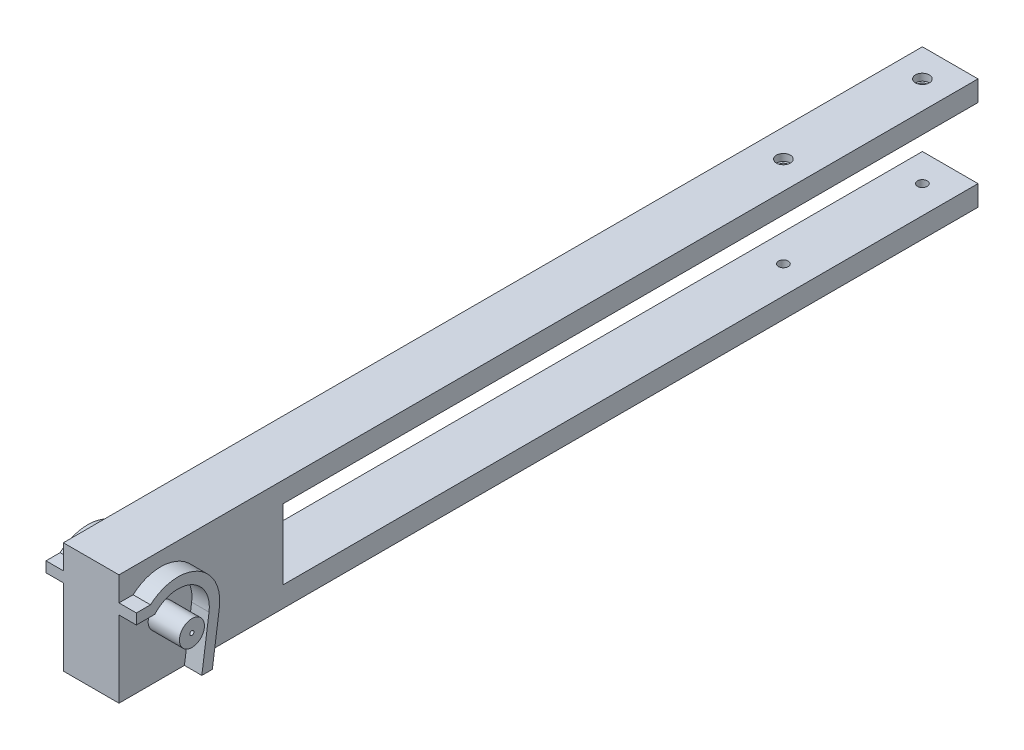
SolidWorks part; units mm, degrees
ref_plane "前视基准面" through (0, 0, 0) normal (0, 0, 1) x (1, 0, 0)
ref_plane "上视基准面" through (0, 0, 0) normal (0, 1, 0) x (1, 0, 0)
ref_plane "右视基准面" through (0, 0, 0) normal (1, 0, 0) x (0, 0, -1)
other "Configuration Table"
sketch "草图2" plane through (0, 0, 0) normal (1, 0, 0) x (0, 0, -1)
  line L0 (-6, 0) -> (17.6, 0) construction
  line L1 (-6, 8) -> (17.6, 8)
  line L2 (-6, 8) -> (-6, -8)
  line L3 (-6, -8) -> (17.6, -8)
  line L4 (17.6, 8) -> (17.6, -8)
  line L5 (1.8, 8) -> (1.8, -8)
  line L6 (4.4562, -0.6263) -> (3.4199, -8)
  line L7 (0, -4.5) -> (-6, -4.5)
  line L8 (0, -4.5) -> (0, 3)
  line L9 (0, 3) -> (-6, 3)
  line L10 (-6, -4.5) -> (-6, 3)
  line L12 (0, 4.5) -> (-6, 4.5)
  line L13 (4.9346, -8) -> (5.9416, -0.835)
  line L14 (0, 5) -> (17.6, 5)
  line L15 (0, 5) -> (0, -5)
  line L16 (0, -5) -> (17.6, -5)
  line L17 (17.6, 5) -> (17.6, -5)
  circle A0 centre (0, 0) radius 1.8
  circle A1 centre (0, 0) radius 4.5
  circle A2 centre (0, 0) radius 6
  dimension "D1" = 3.6
  dimension "D3" = 9
  dimension "D7" = 10
  dimension "D2" = 7.5
  dimension "D4" = 6
  dimension "D5" = 16
  dimension "D6" = 15.8
  dimension "D8" = 82
extrude "凸台-拉伸1" add sketch "草图2" along normal blind 4 contours L1 L4 L3 L2
extrude "凸台-拉伸3" add sketch "草图2<10>" along normal blind 4.5 from surface contours A0 L0 L8 | L8 L0 A0 | L0 L15 A0 | L0 A0 L15 region at (0, -0.7639, -0.7639) region at (0, 0.7639, -0.7639) region at (0, -0.7639, 0.7639) region at (0, 0.7639, 0.7639) starting at face at (4, 0, -5.8)
sketch "草图2<10>" plane through (0, 0, 0) normal (1, 0, 0) x (0, 0, -1) same geometry as "草图2"
sketch "草图5" plane through (8.5, 0, 0) normal (1, 0, 0) x (0, 0, -1)
  circle A0 centre (0, 0) radius 0.3
  dimension "D1" = 0.6
extrude "切除-拉伸10" cut sketch "草图5" against normal blind 1
extrude "凸台-拉伸2" add sketch "草图2<4>" along normal blind 2.5 from surface contours L12 A2 L9 A1 | L5 A2 L12 L15 L14 | A1 L5 L14 L15 | A1 L0 A2 L14 L5 | L14 A2 L5 | L0 A1 L6 A2 | A2 L6 L16 L13 | L16 L6 L3 L13 | A2 L12 L2 L9 region at (0, 2.6915, -4.1879) region at (0, -1.8211, -4.9358) region at (0, 4.6785, -0.9896) region at (0, 5.2074, 0.838) region at (0, 5.2565, -2.3339) region at (0, 3.8249, 3.3838) region at (0, -3.9797, -4.9725) region at (0, 3.8627, 5.2791) region at (0, -6.5, -4.3881) starting at face at (4, 0, -1.8)
sketch "草图2<4>" plane through (0, 0, 0) normal (1, 0, 0) x (0, 0, -1) same geometry as "草图2"
sketch "草图6" plane through (0, 0, -17.6) normal (0, 0, -1) x (-1, 0, 0)
  line L0 (-4, 6) -> (-4, -0.835) construction
  line L1 (0, 8) -> (-4, 8)
  line L2 (0, 8) -> (0, 5.05)
  line L3 (0, 5.05) -> (-4, 5.05)
  line L4 (-4, 8) -> (-4, 5.05)
  line L5 (-4, -0.835) -> (-4, -8) construction
  line L6 (0, -8) -> (-4, -8)
  line L7 (0, -8) -> (0, -5.05)
  line L8 (0, -5.05) -> (-4, -5.05)
  line L9 (-4, -8) -> (-4, -5.05)
  dimension "D1" = 10.1
extrude "凸台-拉伸4" add sketch "草图6" along normal blind 100 contours L8 L9 L6 L7 | L3 L4 L1 L2
mirror "镜向1" about plane through (0, 0, 0) normal (1, 0, 0) of bodies 119 107
sketch "草图7" plane through (0, 8, 0) normal (0, 1, 0) x (1, 0, 0)
  line L0 (-4, 117.6) -> (4, 117.6) construction
  circle A0 centre (0, 113.6) radius 1
  circle A1 centre (0, 113.6) radius 0.7
  circle A2 centre (0, 93.6) radius 1
  circle A3 centre (0, 93.6) radius 0.7
  dimension "D3" = 2
  dimension "D4" = 1.4
  dimension "D1" = 4
  dimension "D2" = 20
extrude "切除-拉伸11" cut sketch "草图7" against normal through all contours A1 | A3
extrude "切除-拉伸12" cut sketch "草图7<3>" against normal blind 1 contours A2 A3 | A0 A1 region at (-0.9717, 8, -113.6) region at (-0.9717, 8, -93.6)
sketch "草图7<3>" plane through (0, 8, 0) normal (0, 1, 0) x (1, 0, 0) same geometry as "草图7"
extrude "切除-拉伸13" cut sketch "草图7<4>" along normal blind 1 from surface contours A2 A3 | A0 A1 region at (-0.9717, 8, -113.6) region at (-0.9717, 8, -93.6) starting at face at (0, -8, -112.9)
sketch "草图7<4>" plane through (0, 8, 0) normal (0, 1, 0) x (1, 0, 0) same geometry as "草图7"
